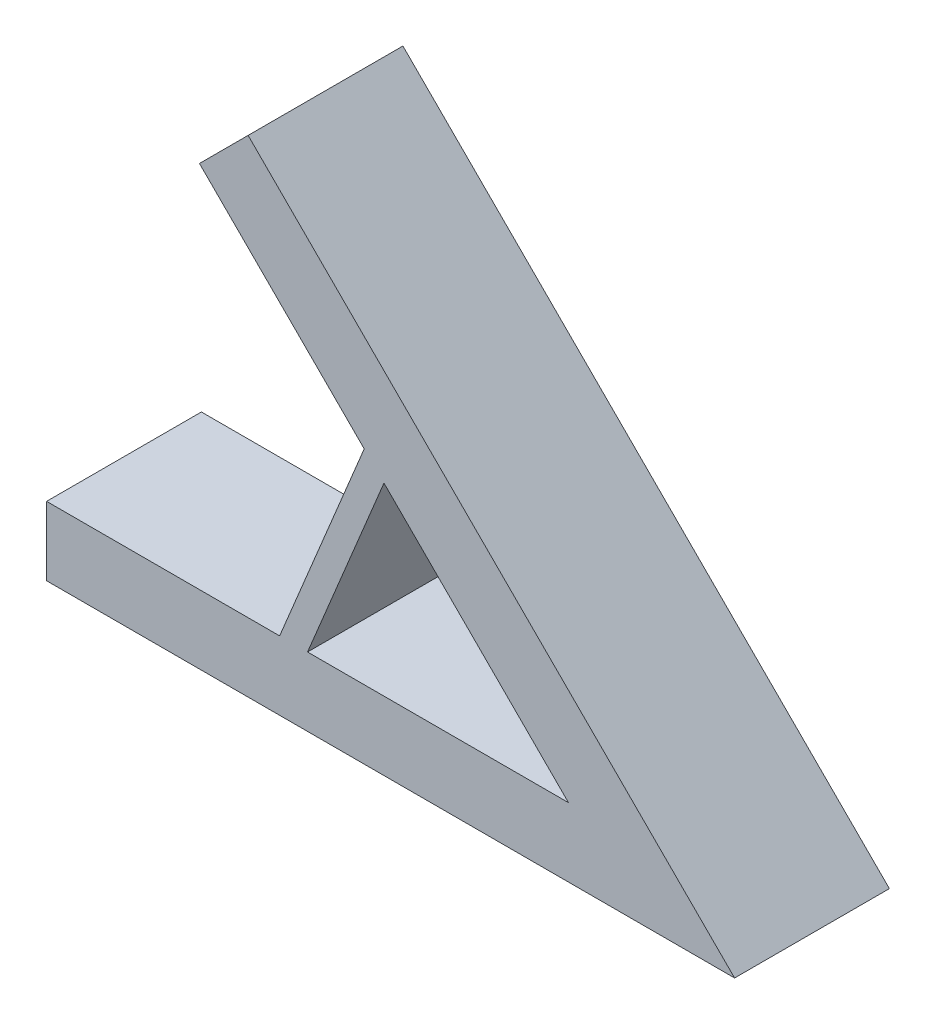
SolidWorks part; units mm, degrees
ref_plane "前视基准面" through (0, 0, 0) normal (0, 0, 1) x (1, 0, 0)
ref_plane "上视基准面" through (0, 0, 0) normal (0, 1, 0) x (1, 0, 0)
ref_plane "右视基准面" through (0, 0, 0) normal (1, 0, 0) x (0, 0, -1)
sketch "草图1" plane through (0, 0, 0) normal (0, 0, 1) x (1, 0, 0)
  line L0 (-80, 0) -> (0, 0)
  line L1 (0, 0) -> (-56.5685, 56.5685)
  line L2 (-56.5685, 56.5685) -> (-62.2254, 50.9117)
  line L3 (-62.2254, 50.9117) -> (-19.3137, 8)
  line L4 (-19.3137, 8) -> (-80, 8)
  line L5 (-80, 8) -> (-80, 0)
  line L6 (-49.6569, 8) -> (-40.7696, 29.4558)
  line L7 (-40.7696, 29.4558) -> (-43.0657, 31.7519)
  line L8 (-43.0657, 31.7519) -> (-52.904, 8)
  line L9 (-52.904, 8) -> (-49.6569, 8)
  dimension "D1" = 45
  dimension "D2" = 80
  dimension "D3" = 80
  dimension "D4" = 8
  dimension "D5" = 8
  dimension "D6" = 3
extrude "凸台-拉伸1" add sketch "草图1" along normal blind 18 contours L4 L5 L0 L1 L2 L3 | L3 L8 L4 L6 region at (-79.0202, 4, 0) region at (-46.6225, 19.3117, 0)
